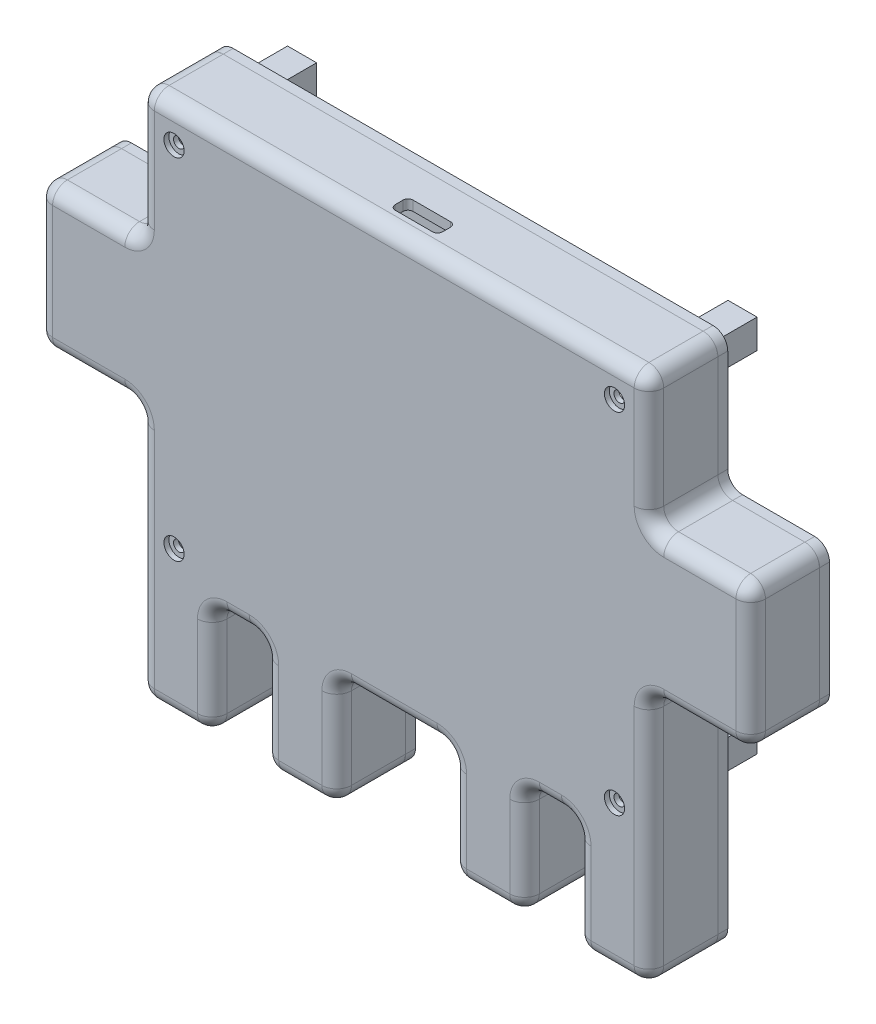
SolidWorks part; units mm, degrees
note: The reader was unsure of these and kept them because the rebuilt part matched: shared geometry of "padTop<8>", "草圖7<4>".
ref_plane "Front Plane" through (0, 0, 0) normal (0, 0, 1) x (1, 0, 0)
ref_plane "Top Plane" through (0, 0, 0) normal (0, 1, 0) x (1, 0, 0)
ref_plane "Right Plane" through (0, 0, 0) normal (1, 0, 0) x (0, 0, -1)
sketch "圖片" plane through (0, 0, 0) normal (0, 0, 1) x (1, 0, 0)
  line L0 (219.174, 501.4094) -> (1128.5073, 501.4094) construction
sketch "padTop" plane through (0, 0, 0) normal (0, 0, 1) x (1, 0, 0)
  line L0 (36.7115, 8.5135) -> (50.8115, 8.5135)
  line L1 (36.7115, 27.6135) -> (50.8115, 27.6135)
  line L2 (36.7115, 27.6135) -> (36.7115, 13.5135)
  line L3 (36.7115, 13.5135) -> (50.8115, 13.5135)
  line L4 (50.8115, 27.6135) -> (50.8115, 13.5135)
  line L5 (36.7115, 27.6135) -> (50.8115, 13.5135) construction
  line L6 (36.7115, 13.5135) -> (50.8115, 27.6135) construction
  line L7 (36.7115, 8.5135) -> (36.7115, -5.5865)
  line L8 (36.7115, -5.5865) -> (50.8115, -5.5865)
  line L9 (50.8115, 8.5135) -> (50.8115, -5.5865)
  line L10 (36.7115, 8.5135) -> (50.8115, -5.5865) construction
  line L11 (36.7115, -5.5865) -> (50.8115, 8.5135) construction
  line L12 (94.0115, 8.5135) -> (108.1115, 8.5135)
  line L13 (94.0115, 27.6135) -> (108.1115, 27.6135)
  line L14 (94.0115, 27.6135) -> (94.0115, 13.5135)
  line L15 (94.0115, 13.5135) -> (108.1115, 13.5135)
  line L16 (108.1115, 27.6135) -> (108.1115, 13.5135)
  line L17 (94.0115, 27.6135) -> (108.1115, 13.5135) construction
  line L18 (94.0115, 13.5135) -> (108.1115, 27.6135) construction
  line L19 (94.0115, 8.5135) -> (94.0115, -5.5865)
  line L20 (94.0115, -5.5865) -> (108.1115, -5.5865)
  line L21 (108.1115, 8.5135) -> (108.1115, -5.5865)
  line L22 (94.0115, 8.5135) -> (108.1115, -5.5865) construction
  line L23 (94.0115, -5.5865) -> (108.1115, 8.5135) construction
  line L24 (55.8115, 8.5135) -> (69.9115, 8.5135)
  line L25 (55.8115, 27.6135) -> (69.9115, 27.6135)
  line L26 (55.8115, 27.6135) -> (55.8115, 13.5135)
  line L27 (55.8115, 13.5135) -> (69.9115, 13.5135)
  line L28 (69.9115, 27.6135) -> (69.9115, 13.5135)
  line L29 (55.8115, 27.6135) -> (69.9115, 13.5135) construction
  line L30 (55.8115, 13.5135) -> (69.9115, 27.6135) construction
  line L31 (55.8115, 8.5135) -> (55.8115, -5.5865)
  line L32 (55.8115, -5.5865) -> (69.9115, -5.5865)
  line L33 (69.9115, 8.5135) -> (69.9115, -5.5865)
  line L34 (55.8115, 8.5135) -> (69.9115, -5.5865) construction
  line L35 (55.8115, -5.5865) -> (69.9115, 8.5135) construction
  line L36 (74.9115, 8.5135) -> (89.0115, 8.5135)
  line L37 (74.9115, 27.6135) -> (89.0115, 27.6135)
  line L38 (74.9115, 27.6135) -> (74.9115, 13.5135)
  line L39 (74.9115, 13.5135) -> (89.0115, 13.5135)
  line L40 (89.0115, 27.6135) -> (89.0115, 13.5135)
  line L41 (74.9115, 27.6135) -> (89.0115, 13.5135) construction
  line L42 (74.9115, 13.5135) -> (89.0115, 27.6135) construction
  line L43 (74.9115, 8.5135) -> (74.9115, -5.5865)
  line L44 (74.9115, -5.5865) -> (89.0115, -5.5865)
  line L45 (89.0115, 8.5135) -> (89.0115, -5.5865)
  line L46 (74.9115, 8.5135) -> (89.0115, -5.5865) construction
  line L47 (74.9115, -5.5865) -> (89.0115, 8.5135) construction
  line L48 (62.8615, 20.5635) -> (81.9615, 20.5635) construction
  line L49 (72.4115, 165.3189) -> (72.4115, -124.1918) construction
  line L50 (81.9615, 20.5635) -> (81.9615, 1.4635) construction
  line L51 (26.7144, 11.0135) -> (137.2086, 11.0135) construction
  line L52 (10.3648, 43.5052) -> (10.3648, 14.3095) construction
  line L53 (33.7615, 30.5635) -> (111.0615, 30.5635)
  line L54 (33.7615, 30.5635) -> (33.7615, -8.5365)
  line L55 (33.7615, -8.5365) -> (111.0615, -8.5365)
  line L56 (111.0615, 30.5635) -> (111.0615, -8.5365)
  line L57 (33.7615, 30.5635) -> (111.0615, -8.5365) construction
  line L58 (33.7615, -8.5365) -> (111.0615, 30.5635) construction
  line L59 (20.6927, 70.4526) -> (124.1303, 70.4526)
  line L60 (20.6927, 70.4526) -> (20.6927, -14.4886)
  line L61 (20.6927, -14.4886) -> (124.1303, -14.4886)
  line L62 (124.1303, 70.4526) -> (124.1303, -14.4886)
  line L63 (20.6927, 70.4526) -> (124.1303, -14.4886) construction
  line L64 (20.6927, -14.4886) -> (124.1303, 70.4526) construction
  line L65 (20.6927, 43.5052) -> (0.037, 43.5052)
  line L66 (20.6927, 43.5052) -> (20.6927, 14.3095)
  line L67 (20.6927, 14.3095) -> (0.037, 14.3095)
  line L68 (0.037, 43.5052) -> (0.037, 14.3095)
  line L69 (124.1303, 43.6826) -> (144.7861, 43.6826)
  line L70 (124.1303, 43.6826) -> (124.1303, 14.487)
  line L71 (124.1303, 14.487) -> (144.7861, 14.487)
  line L72 (144.7861, 43.6826) -> (144.7861, 14.487)
  line L73 (20.6927, -14.4886) -> (35.4563, -14.4886)
  line L74 (20.6927, -14.4886) -> (20.6927, -37.1354)
  line L75 (20.6927, -37.1354) -> (35.4563, -37.1354)
  line L76 (35.4563, -14.4886) -> (35.4563, -37.1354)
  line L77 (45.9563, -14.4886) -> (60.7199, -14.4886)
  line L78 (45.9563, -14.4886) -> (45.9563, -37.1354)
  line L79 (45.9563, -37.1354) -> (60.7199, -37.1354)
  line L80 (60.7199, -14.4886) -> (60.7199, -37.1354)
  line L81 (84.1032, -14.4886) -> (98.8668, -14.4886)
  line L82 (84.1032, -14.4886) -> (84.1032, -37.1354)
  line L83 (84.1032, -37.1354) -> (98.8668, -37.1354)
  line L84 (98.8668, -14.4886) -> (98.8668, -37.1354)
  line L85 (124.1303, -14.4886) -> (109.3668, -14.4886)
  line L86 (124.1303, -14.4886) -> (124.1303, -37.1354)
  line L87 (124.1303, -37.1354) -> (109.3668, -37.1354)
  line L88 (109.3668, -14.4886) -> (109.3668, -37.1354)
  line L89 (37.3633, 56.7764) -> (48.4633, 56.7764)
  line L90 (37.3633, 56.7764) -> (37.3633, 45.6764)
  line L91 (37.3633, 45.6764) -> (48.4633, 45.6764)
  line L92 (48.4633, 56.7764) -> (48.4633, 45.6764)
  line L93 (37.3633, 56.7764) -> (48.4633, 45.6764) construction
  line L94 (37.3633, 45.6764) -> (48.4633, 56.7764) construction
  line L95 (96.5235, 56.7764) -> (107.6235, 56.7764)
  line L96 (96.5235, 56.7764) -> (96.5235, 45.6764)
  line L97 (96.5235, 45.6764) -> (107.6235, 45.6764)
  line L98 (107.6235, 56.7764) -> (107.6235, 45.6764)
  line L99 (96.5235, 56.7764) -> (107.6235, 45.6764) construction
  line L100 (96.5235, 45.6764) -> (107.6235, 56.7764) construction
  line L105 (201129.9861, 29.0848) -> (-248870.0139, 29.0848) construction
  line L106 (122.9361, 36.1348) -> (137.0361, 36.1348)
  line L107 (-989.8311, 29.0848) -> (49010.1689, 29.0848) construction
  line L108 (139.9861, 38.7911) -> (119.9861, 38.7911)
  line L109 (139.9861, 38.7911) -> (139.9861, 19.3785)
  line L110 (139.9861, 19.3785) -> (119.9861, 19.3785)
  line L111 (119.9861, 38.7911) -> (119.9861, 19.3785)
  line L112 (139.9861, 38.7911) -> (119.9861, 19.3785) construction
  line L113 (139.9861, 19.3785) -> (119.9861, 38.7911) construction
  line L114 (43.7615, 20.5635) -> (62.8615, 20.5635) construction
  line L115 (32.9133, 61.2264) -> (52.9133, 61.2264)
  line L116 (32.9133, 61.2264) -> (32.9133, 41.2264)
  line L117 (32.9133, 41.2264) -> (52.9133, 41.2264)
  line L118 (52.9133, 61.2264) -> (52.9133, 41.2264)
  line L119 (32.9133, 61.2264) -> (52.9133, 41.2264) construction
  line L120 (32.9133, 41.2264) -> (52.9133, 61.2264) construction
  line L121 (92.0735, 61.2264) -> (112.0735, 61.2264)
  line L122 (92.0735, 61.2264) -> (92.0735, 41.2264)
  line L123 (92.0735, 41.2264) -> (112.0735, 41.2264)
  line L124 (112.0735, 61.2264) -> (112.0735, 41.2264)
  line L125 (92.0735, 61.2264) -> (112.0735, 41.2264) construction
  line L126 (92.0735, 41.2264) -> (112.0735, 61.2264) construction
  line L127 (81.9615, 20.5635) -> (101.0615, 20.5635) construction
  line L128 (53.3115, 20.5635) -> (53.3115, 3.2406) construction
  line L129 (91.5115, 20.5635) -> (91.5115, 3.2406) construction
  line L130 (124.1303, 43.6826) -> (144.7861, 43.6826) construction
  line L131 (20.6927, 43.5052) -> (0.037, 43.5052) construction
  line L132 (124.1303, 14.487) -> (144.7861, 14.487) construction
  line L133 (122.9361, 36.1348) -> (122.9361, 22.0348)
  line L134 (122.9361, 22.0348) -> (137.0361, 22.0348)
  line L135 (137.0361, 36.1348) -> (137.0361, 22.0348)
  line L136 (122.9361, 36.1348) -> (137.0361, 22.0348) construction
  line L137 (122.9361, 22.0348) -> (137.0361, 36.1348) construction
  circle A1 centre (14.837, 29.0848) radius 4.5
  point P0 (43.7615, 20.5635)
  point P5 (43.7615, 1.4635)
  point P10 (72.4115, 11.0135)
  point P11 (101.0615, 20.5635)
  point P16 (101.0615, 1.4635)
  point P21 (62.8615, 20.5635)
  point P26 (62.8615, 1.4635)
  point P31 (81.9615, 20.5635)
  point P36 (81.9615, 1.4635)
  point P45 (72.4115, 20.5635)
  point P46 (72.4115, 20.5635)
  point P50 (81.9615, 11.0135)
  point P51 (72.4115, 11.0135)
  point P56 (72.4115, 27.982)
  point P83 (42.9133, 51.2264)
  point P88 (102.0735, 51.2264)
  point P95 (129.9861, 29.0848)
  point P96 (129.9861, 29.0848)
  point P109 (124.7964, 29.0848)
  point P110 (102.0735, 51.2264)
  point P111 (42.9133, 51.2264)
  point P120 (0, 0)
  point P121 (129.9861, 29.0848)
  point P128 (53.3115, 11.0135)
  point P129 (91.5115, 11.0135)
  dimension "D8" = 10.5
  dimension "D16" = 14.1
  dimension "D13" = 9
  dimension "D1" = 14.1
  dimension "D2" = 19.1
  dimension "D3" = 19.1
  dimension "D4" = 19.1
  dimension "D5" = 19.1
  dimension "D6" = 10
  dimension "D7" = 10
  dimension "D9" = 10.5
  dimension "D10" = 11.1
  dimension "D11" = 14.8
  dimension "D12" = 20
  dimension "D14" = 14.8
  dimension "D15" = 20
  dimension "D17" = 103.4376
sketch "RP2024" plane through (0, 0, 0) normal (0, 0, 1) x (1, 0, 0)
  line L0 (20.6927, 70.4526) -> (124.1303, 70.4526) construction
  line L1 (60.8615, 68.2526) -> (83.9615, 68.2526) construction
  line L2 (60.8615, 68.2526) -> (60.8615, 14.7526) construction
  line L3 (60.8615, 14.7526) -> (83.9615, 14.7526) construction
  line L4 (83.9615, 68.2526) -> (83.9615, 14.7526) construction
  line L5 (60.8615, 68.2526) -> (83.9615, 14.7526) construction
  line L6 (60.8615, 14.7526) -> (83.9615, 68.2526) construction
  line L7 (72.4115, 165.3189) -> (72.4115, -124.1918) construction
  point P0 (72.4115, 41.5026)
  dimension "D1" = 53.5
  dimension "D2" = 23.1
  dimension "D3" = 2.2
sketch "numb" plane through (0, 0, 0) normal (0, 0, 1) x (1, 0, 0)
  circle A1 centre (14.837, 29.0848) radius 17.5
  dimension "D2" = 35
extrude "填料-伸長1" add sketch "padTop" along normal blind 3
extrude "填料-伸長4" add sketch "padTop<8>" against normal blind 2
sketch "padTop<8>" plane through (0, 0, 0) normal (0, 0, 1) x (1, 0, 0) same geometry as "padTop"
sketch "草圖2" plane through (0, 0, 0) normal (0, 0, 1) x (1, 0, 0)
  line L0 (20.6927, 43.5052) -> (0.037, 43.5052)
  line L5 (0.037, 43.5052) -> (0.037, 14.3095)
  line L6 (0.037, 14.3095) -> (20.6927, 14.3095)
  line L31 (20.6927, 14.3095) -> (20.6927, -37.1354)
  line L32 (20.6927, -37.1354) -> (35.4563, -37.1354)
  line L33 (35.4563, -37.1354) -> (35.4563, -14.4886)
  line L34 (35.4563, -14.4886) -> (45.9563, -14.4886)
  line L35 (45.9563, -14.4886) -> (45.9563, -37.1354)
  line L36 (45.9563, -37.1354) -> (60.7199, -37.1354)
  line L37 (60.7199, -37.1354) -> (60.7199, -14.4886)
  line L38 (60.7199, -14.4886) -> (84.1032, -14.4886)
  line L39 (84.1032, -14.4886) -> (84.1032, -37.1354)
  line L40 (84.1032, -37.1354) -> (98.8668, -37.1354)
  line L41 (98.8668, -37.1354) -> (98.8668, -14.4886)
  line L42 (98.8668, -14.4886) -> (109.3668, -14.4886)
  line L43 (109.3668, -14.4886) -> (109.3668, -37.1354)
  line L44 (109.3668, -37.1354) -> (124.1303, -37.1354)
  line L45 (124.1303, -37.1354) -> (124.1303, 14.487)
  line L46 (124.1303, 14.487) -> (144.7861, 14.487)
  line L47 (144.7861, 14.487) -> (144.7861, 43.6826)
  line L48 (144.7861, 43.6826) -> (124.1303, 43.6826)
  line L49 (124.1303, 43.6826) -> (124.1303, 70.4526)
  line L50 (124.1303, 70.4526) -> (20.6927, 70.4526)
  line L51 (20.6927, 70.4526) -> (20.6927, 43.5052)
extrude "填料-伸長6" add sketch "草圖2" along normal blind 14 separate body
fillet "圓角2" radius 3 48 edges at (72.4115, 70.4526, 14) (124.1303, 57.0676, 14) (134.4582, 43.6826, 14) (144.7861, 29.0848, 14) (134.4582, 14.487, 14) (124.1303, -11.3242, 14) (116.7485, -37.1354, 14) (109.3668, -25.812, 14) (104.1168, -14.4886, 14) (98.8668, -25.812, 14) (91.485, -37.1354, 14) (84.1032, -25.812, 14) (72.4115, -14.4886, 14) (60.7199, -25.812, 14) (53.3381, -37.1354, 14) (45.9563, -25.812, 14) (40.7063, -14.4886, 14) (35.4563, -25.812, 14) (28.0745, -37.1354, 14) (20.6927, -11.4129, 14) (10.3648, 14.3095, 14) (0.037, 28.9073, 14) (10.3648, 43.5052, 14) (20.6927, 56.9789, 14) (20.6927, 70.4526, 7) (20.6927, 43.5052, 7) (0.037, 43.5052, 7) (35.4563, -14.4886, 7) (35.4563, -37.1354, 7) (0.037, 14.3095, 7) (20.6927, 14.3095, 7) (20.6927, -37.1354, 7) (45.9563, -14.4886, 7) (45.9563, -37.1354, 7) (60.7199, -37.1354, 7) (60.7199, -14.4886, 7) (98.8668, -14.4886, 7) (98.8668, -37.1354, 7) (84.1032, -37.1354, 7) (84.1032, -14.4886, 7) (109.3668, -14.4886, 7) (109.3668, -37.1354, 7) (124.1303, -37.1354, 7) (124.1303, 14.487, 7) (144.7861, 14.487, 7) (144.7861, 43.6826, 7) (124.1303, 43.6826, 7) (124.1303, 70.4526, 7)
shell "薄殼1" thickness 2
fillet "圓角4" radius 3 48 edges at (35.4563, -37.1354, 0.5) (20.6927, -37.1354, 0.5) (35.4563, -25.812, 3) (28.0745, -37.1354, 3) (60.7199, -37.1354, 0.5) (45.9563, -37.1354, 0.5) (45.9563, -25.812, 3) (60.7199, -25.812, 3) (53.3381, -37.1354, 3) (98.8668, -37.1354, 0.5) (84.1032, -37.1354, 0.5) (84.1032, -25.812, 3) (98.8668, -25.812, 3) (91.485, -37.1354, 3) (124.1303, -37.1354, 0.5) (109.3668, -37.1354, 0.5) (109.3668, -25.812, 3) (116.7485, -37.1354, 3) (134.4582, 43.6826, 3) (124.1303, 57.0676, 3) (72.4115, 70.4526, 3) (20.6927, 56.9789, 3) (10.3648, 43.5052, 3) (144.7861, 43.6826, 0.5) (144.7861, 14.487, 0.5) (124.1303, 14.487, 0.5) (0.037, 28.9073, 3) (20.6927, 14.3095, 0.5) (0.037, 14.3095, 0.5) (0.037, 43.5052, 0.5) (20.6927, 43.5052, 0.5) (20.6927, 70.4526, 0.5) (124.1303, 70.4526, 0.5) (124.1303, 43.6826, 0.5) (10.3648, 14.3095, 3) (20.6927, -11.4129, 3) (124.1303, -11.3242, 3) (134.4582, 14.487, 3) (40.7063, -14.4886, 3) (72.4115, -14.4886, 3) (144.7861, 29.0848, 3) (104.1168, -14.4886, 3) (109.3668, -14.4886, 0.5) (98.8668, -14.4886, 0.5) (84.1032, -14.4886, 0.5) (60.7199, -14.4886, 0.5) (45.9563, -14.4886, 0.5) (35.4563, -14.4886, 0.5)
ref_plane "平面1" through (0, 0, 12) normal (0, 0, -1) x (-1, 0, 0)
sketch "草圖4" plane through (0, 0, 12) normal (0, 0, -1) x (-1, 0, 0)
  line L0 (-92.5115, 16.0135) -> (-90.5115, 16.0135)
  line L1 (-54.3115, 16.0135) -> (-52.3115, 16.0135)
  line L4 (-54.3115, 16.0135) -> (-54.3115, 6.0135)
  line L5 (-54.3115, 6.0135) -> (-52.3115, 6.0135)
  line L6 (-52.3115, 16.0135) -> (-52.3115, 6.0135)
  line L7 (-54.3115, 16.0135) -> (-52.3115, 6.0135) construction
  line L8 (-54.3115, 6.0135) -> (-52.3115, 16.0135) construction
  line L9 (-58.3115, 12.0135) -> (-48.3115, 12.0135)
  line L10 (-58.3115, 12.0135) -> (-58.3115, 10.0135)
  line L11 (-58.3115, 10.0135) -> (-48.3115, 10.0135)
  line L12 (-48.3115, 12.0135) -> (-48.3115, 10.0135)
  line L13 (-58.3115, 12.0135) -> (-48.3115, 10.0135) construction
  line L14 (-58.3115, 10.0135) -> (-48.3115, 12.0135) construction
  line L15 (-92.5115, 16.0135) -> (-92.5115, 6.0135)
  line L16 (-92.5115, 6.0135) -> (-90.5115, 6.0135)
  line L17 (-90.5115, 16.0135) -> (-90.5115, 6.0135)
  line L18 (-92.5115, 16.0135) -> (-90.5115, 6.0135) construction
  line L19 (-92.5115, 6.0135) -> (-90.5115, 16.0135) construction
  line L20 (-96.5115, 12.0135) -> (-86.5115, 12.0135)
  line L21 (-96.5115, 12.0135) -> (-96.5115, 10.0135)
  line L22 (-96.5115, 10.0135) -> (-86.5115, 10.0135)
  line L23 (-86.5115, 12.0135) -> (-86.5115, 10.0135)
  line L24 (-96.5115, 12.0135) -> (-86.5115, 10.0135) construction
  line L25 (-96.5115, 10.0135) -> (-86.5115, 12.0135) construction
  point P0 (-53.3115, 11.0135)
  point P5 (-53.3115, 11.0135)
  point P11 (-91.5115, 11.0135)
  point P17 (-91.5115, 11.0135)
  dimension "D1" = 10
  dimension "D2" = 2
ref_plane "平面2" through (0, 0, -2) normal (0, 0, 1) x (1, 0, 0)
sketch "草圖5" plane through (0, 0, -2) normal (0, 0, 1) x (1, 0, 0)
  line L1 (26.7427, 64.4026) -> (28.6427, 64.4026)
  line L2 (26.7427, 64.4026) -> (26.7427, 62.5026)
  line L3 (26.7427, 62.5026) -> (28.6427, 62.5026)
  line L4 (28.6427, 64.4026) -> (28.6427, 62.5026)
  line L5 (26.7427, 64.4026) -> (28.6427, 62.5026) construction
  line L6 (26.7427, 62.5026) -> (28.6427, 64.4026) construction
  line L7 (20.6927, 70.4526) -> (20.6927, -14.4886) construction
  line L8 (26.7427, -6.5386) -> (28.6427, -6.5386)
  line L9 (24.7427, 66.4026) -> (30.6427, 66.4026)
  line L10 (24.7427, 66.4026) -> (24.7427, 60.5026)
  line L11 (24.7427, 60.5026) -> (30.6427, 60.5026)
  line L12 (30.6427, 66.4026) -> (30.6427, 60.5026)
  line L13 (24.7427, 66.4026) -> (30.6427, 60.5026) construction
  line L14 (24.7427, 60.5026) -> (30.6427, 66.4026) construction
  line L15 (26.7427, -6.5386) -> (26.7427, -8.4386)
  line L16 (26.7427, -8.4386) -> (28.6427, -8.4386)
  line L17 (28.6427, -6.5386) -> (28.6427, -8.4386)
  line L18 (26.7427, -6.5386) -> (28.6427, -8.4386) construction
  line L19 (26.7427, -8.4386) -> (28.6427, -6.5386) construction
  line L20 (24.7427, -4.5386) -> (30.6427, -4.5386)
  line L21 (24.7427, -4.5386) -> (24.7427, -10.4386)
  line L22 (24.7427, -10.4386) -> (30.6427, -10.4386)
  line L23 (30.6427, -4.5386) -> (30.6427, -10.4386)
  line L24 (24.7427, -4.5386) -> (30.6427, -10.4386) construction
  line L25 (24.7427, -10.4386) -> (30.6427, -4.5386) construction
  line L26 (116.1803, -6.5386) -> (118.0803, -6.5386)
  line L27 (116.1803, -6.5386) -> (116.1803, -8.4386)
  line L28 (116.1803, -8.4386) -> (118.0803, -8.4386)
  line L29 (118.0803, -6.5386) -> (118.0803, -8.4386)
  line L30 (116.1803, -6.5386) -> (118.0803, -8.4386) construction
  line L31 (116.1803, -8.4386) -> (118.0803, -6.5386) construction
  line L32 (114.1803, -4.5386) -> (120.0803, -4.5386)
  line L33 (114.1803, -4.5386) -> (114.1803, -10.4386)
  line L34 (114.1803, -10.4386) -> (120.0803, -10.4386)
  line L35 (120.0803, -4.5386) -> (120.0803, -10.4386)
  line L36 (114.1803, -4.5386) -> (120.0803, -10.4386) construction
  line L37 (114.1803, -10.4386) -> (120.0803, -4.5386) construction
  line L38 (116.1803, 64.4026) -> (118.0803, 64.4026)
  line L39 (116.1803, 64.4026) -> (116.1803, 62.5026)
  line L40 (116.1803, 62.5026) -> (118.0803, 62.5026)
  line L41 (118.0803, 64.4026) -> (118.0803, 62.5026)
  line L42 (116.1803, 64.4026) -> (118.0803, 62.5026) construction
  line L43 (116.1803, 62.5026) -> (118.0803, 64.4026) construction
  line L44 (114.1803, 66.4026) -> (120.0803, 66.4026)
  line L45 (114.1803, 66.4026) -> (114.1803, 60.5026)
  line L46 (114.1803, 60.5026) -> (120.0803, 60.5026)
  line L47 (120.0803, 66.4026) -> (120.0803, 60.5026)
  line L48 (114.1803, 66.4026) -> (120.0803, 60.5026) construction
  line L49 (114.1803, 60.5026) -> (120.0803, 66.4026) construction
  line L50 (52.3115, 16.0135) -> (54.3115, 16.0135)
  line L51 (20.6927, 70.4526) -> (124.1303, 70.4526) construction
  line L52 (20.6927, -14.4886) -> (124.1303, -14.4886) construction
  line L53 (124.1303, 70.4526) -> (124.1303, -14.4886) construction
  line L54 (52.3115, 16.0135) -> (52.3115, 6.0135)
  line L55 (52.3115, 6.0135) -> (54.3115, 6.0135)
  line L56 (54.3115, 16.0135) -> (54.3115, 6.0135)
  line L57 (48.3115, 12.0135) -> (58.3115, 12.0135)
  line L58 (48.3115, 12.0135) -> (48.3115, 10.0135)
  line L59 (48.3115, 10.0135) -> (58.3115, 10.0135)
  line L60 (58.3115, 12.0135) -> (58.3115, 10.0135)
  line L61 (86.5115, 12.0135) -> (96.5115, 12.0135)
  line L62 (86.5115, 12.0135) -> (86.5115, 10.0135)
  line L63 (86.5115, 10.0135) -> (96.5115, 10.0135)
  line L64 (96.5115, 12.0135) -> (96.5115, 10.0135)
  line L65 (92.5115, 16.0135) -> (90.5115, 16.0135)
  line L66 (92.5115, 16.0135) -> (92.5115, 6.0135)
  line L67 (92.5115, 6.0135) -> (90.5115, 6.0135)
  line L68 (90.5115, 16.0135) -> (90.5115, 6.0135)
  point P0 (27.6927, 63.4526)
  point P5 (27.6927, 63.4526)
  point P14 (27.6927, -7.4886)
  point P19 (27.6927, -7.4886)
  point P24 (117.1303, -7.4886)
  point P29 (117.1303, -7.4886)
  point P34 (117.1303, 63.4526)
  point P39 (117.1303, 63.4526)
  dimension "D1" = 1.9
  dimension "D2" = 7
  dimension "D3" = 7
  dimension "D4" = 5.9
  dimension "D5" = 7
  dimension "D6" = 7
extrude "填料-伸長9" add sketch "草圖5" against normal blind 10 contours L61 L68 L63 L66 | L68 L61 L62 L63 | L65 L68 L61 L66 | L63 L68 L67 L66 | L61 L66 L63 L64 | L54 L59 L56 L57 | L58 L59 L54 L57 | L54 L57 L56 L50 | L60 L57 L56 L59 | L59 L54 L55 L56 | L23 L20 L21 L22 L8 L17 L16 L15 | L35 L32 L33 L34 L26 L29 L28 L27 | L47 L44 L45 L46 L38 L41 L40 L39 | L12 L9 L10 L11 L1 L4 L3 L2
ref_plane "平面3" through (0, 0, 14) normal (0, 0, 1) x (1, 0, 0)
sketch "草圖7" plane through (0, 0, 14) normal (0, 0, 1) x (1, 0, 0)
  line L0 (26.7427, -6.5386) -> (28.6427, -8.4386) construction
  circle A0 centre (27.6927, 63.4526) radius 2.05
  circle A1 centre (117.1303, 63.4526) radius 2.05
  circle A2 centre (117.1303, -7.4886) radius 2.05
  circle A3 centre (27.6927, -7.4886) radius 2.05
  circle A4 centre (27.6927, 63.4526) radius 1.1
  circle A5 centre (117.1303, 63.4526) radius 1.1
  circle A6 centre (117.1303, -7.4886) radius 1.1
  circle A7 centre (27.6927, -7.4886) radius 1.1
  dimension "D1" = 4.1
  dimension "D2" = 2.2
extrude "除料-伸長1" cut sketch "草圖7" against normal up to next (2 mm away) contours A6 | A4 | A5 | A7
extrude "除料-伸長2" cut sketch "草圖7<4>" against normal blind 1
sketch "草圖7<4>" plane through (0, 0, 14) normal (0, 0, 1) x (1, 0, 0) same geometry as "草圖7"
ref_plane "平面4" through (0, 70.4526, 0) normal (0, 1, 0) x (1, 0, 0)
sketch "草圖10" plane through (0, 70.4526, 0) normal (0, 1, 0) x (1, 0, 0)
  line L0 (72.4115, 0) -> (72.4115, -14) construction
  line L1 (-55.8734, -14) -> (55.8734, -14) construction
  line L7 (67.6115, -6.4) -> (77.2115, -6.4)
  line L8 (67.6115, -6.4) -> (67.6115, -10)
  line L9 (67.6115, -10) -> (77.2115, -10)
  line L10 (77.2115, -6.4) -> (77.2115, -10)
  line L11 (67.6115, -6.4) -> (77.2115, -10) construction
  line L12 (67.6115, -10) -> (77.2115, -6.4) construction
  point P5 (72.4115, -8.2)
  dimension "D1" = 3.6
  dimension "D2" = 9.6
  dimension "D3" = 4
extrude "除料-伸長3" cut sketch "草圖10" against normal up to next (2 mm away)
fillet "圓角5" radius 1 4 edges at (67.6115, 69.4526, 6.4) (67.6115, 69.4526, 10) (77.2115, 69.4526, 6.4) (77.2115, 69.4526, 10)
ref_plane "平面5" through (0, 0, 12) normal (0, 0, -1) x (-1, 0, 0)
sketch "草圖12" plane through (0, 0, 12) normal (0, 0, -1) x (-1, 0, 0)
  line L0 (-60.8615, 68.2526) -> (-60.8615, 14.7526) construction
  line L1 (-60.6615, 67.9526) -> (-59.6615, 67.9526)
  line L2 (-60.6615, 67.9526) -> (-60.6615, 64.9526)
  line L3 (-60.6615, 64.9526) -> (-59.6615, 64.9526)
  line L4 (-59.6615, 67.9526) -> (-59.6615, 64.9526)
  line L5 (-60.6615, 67.9526) -> (-59.6615, 64.9526) construction
  line L6 (-60.6615, 64.9526) -> (-59.6615, 67.9526) construction
  line L7 (-85.1615, 67.9526) -> (-84.1615, 67.9526)
  line L8 (-85.1615, 67.9526) -> (-85.1615, 64.9526)
  line L9 (-85.1615, 64.9526) -> (-84.1615, 64.9526)
  line L10 (-84.1615, 67.9526) -> (-84.1615, 64.9526)
  line L11 (-85.1615, 67.9526) -> (-84.1615, 64.9526) construction
  line L12 (-85.1615, 64.9526) -> (-84.1615, 67.9526) construction
  line L13 (-20.6927, 70.4526) -> (-124.1303, 70.4526) construction
  line L14 (-83.9615, 68.2526) -> (-83.9615, 14.7526) construction
  line L15 (-85.1615, 14.5526) -> (-82.1615, 14.5526)
  line L16 (-60.6615, 13.5526) -> (-59.6615, 13.5526)
  line L17 (-60.6615, 13.5526) -> (-60.6615, 16.5526)
  line L18 (-60.6615, 16.5526) -> (-59.6615, 16.5526)
  line L19 (-59.6615, 13.5526) -> (-59.6615, 16.5526)
  line L20 (-60.6615, 13.5526) -> (-59.6615, 16.5526) construction
  line L21 (-60.6615, 16.5526) -> (-59.6615, 13.5526) construction
  line L22 (-62.6615, 14.5526) -> (-59.6615, 14.5526)
  line L23 (-62.6615, 14.5526) -> (-62.6615, 13.5526)
  line L24 (-62.6615, 13.5526) -> (-59.6615, 13.5526)
  line L25 (-59.6615, 14.5526) -> (-59.6615, 13.5526)
  line L26 (-62.6615, 14.5526) -> (-59.6615, 13.5526) construction
  line L27 (-62.6615, 13.5526) -> (-59.6615, 14.5526) construction
  line L28 (-85.1615, 16.5526) -> (-84.1615, 16.5526)
  line L29 (-85.1615, 16.5526) -> (-85.1615, 13.5526)
  line L30 (-85.1615, 13.5526) -> (-84.1615, 13.5526)
  line L31 (-84.1615, 16.5526) -> (-84.1615, 13.5526)
  line L32 (-85.1615, 16.5526) -> (-84.1615, 13.5526) construction
  line L33 (-85.1615, 13.5526) -> (-84.1615, 16.5526) construction
  line L34 (-85.1615, 14.5526) -> (-85.1615, 13.5526)
  line L35 (-85.1615, 13.5526) -> (-82.1615, 13.5526)
  line L36 (-82.1615, 14.5526) -> (-82.1615, 13.5526)
  line L37 (-85.1615, 14.5526) -> (-82.1615, 13.5526) construction
  line L38 (-85.1615, 13.5526) -> (-82.1615, 14.5526) construction
  line L39 (-60.8615, 14.7526) -> (-83.9615, 14.7526) construction
  line L41 (-20.737, 35.1348) -> (-8.937, 35.1348)
  line L42 (-20.737, 35.1348) -> (-20.737, 23.0348)
  line L43 (-20.737, 23.0348) -> (-8.937, 23.0348)
  line L44 (-8.937, 35.1348) -> (-8.937, 23.0348)
  line L45 (-20.737, 35.1348) -> (-8.937, 23.0348) construction
  line L46 (-20.737, 23.0348) -> (-8.937, 35.1348) construction
  line L47 (-21.837, 36.2348) -> (-20.837, 36.2348)
  line L48 (-21.837, 36.2348) -> (-21.837, 34.2348)
  line L49 (-21.837, 34.2348) -> (-20.837, 34.2348)
  line L50 (-20.837, 36.2348) -> (-20.837, 34.2348)
  line L51 (-21.837, 36.2348) -> (-20.837, 34.2348) construction
  line L52 (-21.837, 34.2348) -> (-20.837, 36.2348) construction
  line L53 (-21.837, 36.2348) -> (-19.837, 36.2348)
  line L54 (-21.837, 36.2348) -> (-21.837, 35.2348)
  line L55 (-21.837, 35.2348) -> (-19.837, 35.2348)
  line L56 (-19.837, 36.2348) -> (-19.837, 35.2348)
  line L57 (-9.837, 36.2348) -> (-7.837, 36.2348)
  line L58 (-9.837, 36.2348) -> (-9.837, 35.2348)
  line L59 (-9.837, 35.2348) -> (-7.837, 35.2348)
  line L60 (-7.837, 36.2348) -> (-7.837, 35.2348)
  line L61 (-7.837, 36.2348) -> (-8.837, 36.2348)
  line L62 (-7.837, 36.2348) -> (-7.837, 34.2348)
  line L63 (-7.837, 34.2348) -> (-8.837, 34.2348)
  line L64 (-8.837, 36.2348) -> (-8.837, 34.2348)
  line L65 (-8.837, 23.9348) -> (-7.837, 23.9348)
  line L66 (-8.837, 23.9348) -> (-8.837, 21.9348)
  line L67 (-8.837, 21.9348) -> (-7.837, 21.9348)
  line L68 (-7.837, 23.9348) -> (-7.837, 21.9348)
  line L69 (-7.837, 21.9348) -> (-9.837, 21.9348)
  line L70 (-7.837, 21.9348) -> (-7.837, 22.9348)
  line L71 (-7.837, 22.9348) -> (-9.837, 22.9348)
  line L72 (-9.837, 21.9348) -> (-9.837, 22.9348)
  line L73 (-21.837, 23.9348) -> (-20.837, 23.9348)
  line L74 (-21.837, 23.9348) -> (-21.837, 21.9348)
  line L75 (-21.837, 21.9348) -> (-20.837, 21.9348)
  line L76 (-20.837, 23.9348) -> (-20.837, 21.9348)
  line L77 (-21.837, 21.9348) -> (-19.837, 21.9348)
  line L78 (-21.837, 21.9348) -> (-21.837, 22.9348)
  line L79 (-21.837, 22.9348) -> (-19.837, 22.9348)
  line L80 (-19.837, 21.9348) -> (-19.837, 22.9348)
  point P0 (-60.1615, 66.4526)
  point P5 (-84.6615, 66.4526)
  point P12 (-60.1615, 67.9526)
  point P17 (-61.1615, 14.0526)
  point P18 (-60.1615, 15.0526)
  point P27 (-84.6615, 15.0526)
  point P32 (-83.6615, 14.0526)
  point P37 (-21.337, 35.2348)
  point P44 (-14.837, 29.0848)
  point P74 (0, 0)
  point P75 (0, 0)
  point P76 (0, 0)
  point P77 (0, 0)
  point P78 (0, 0)
  dimension "D1" = 1
  dimension "D2" = 3
  dimension "D3" = 0.2
  dimension "D4" = 2.5
  dimension "D5" = 0.2
  dimension "D6" = 0.2
  dimension "D7" = 12.1
  dimension "D8" = 11.8
  dimension "D9" = 0.1
  dimension "D10" = 2
  dimension "D11" = 1
  dimension "D12" = 0.1
  dimension "D13" = 0.1
  dimension "D14" = 0.1
extrude "填料-伸長10" add sketch "草圖12" along normal blind 5 contours L31 L28 L29 L15 | L36 L15 L31 L35 | L31 L15 L29 L30 | L23 L24 L17 L22 | L22 L17 L16 L19 | L17 L22 L19 L18 | L4 L1 L2 L3 | L10 L7 L8 L9 | L54 L53 L56 L55 | L48 L47 L50 L49 | L58 L57 L60 L59 | L62 L61 L64 L63 | L66 L65 L68 L67 | L70 L69 L72 L71 | L78 L77 L80 L79 | L74 L73 L76 L75
